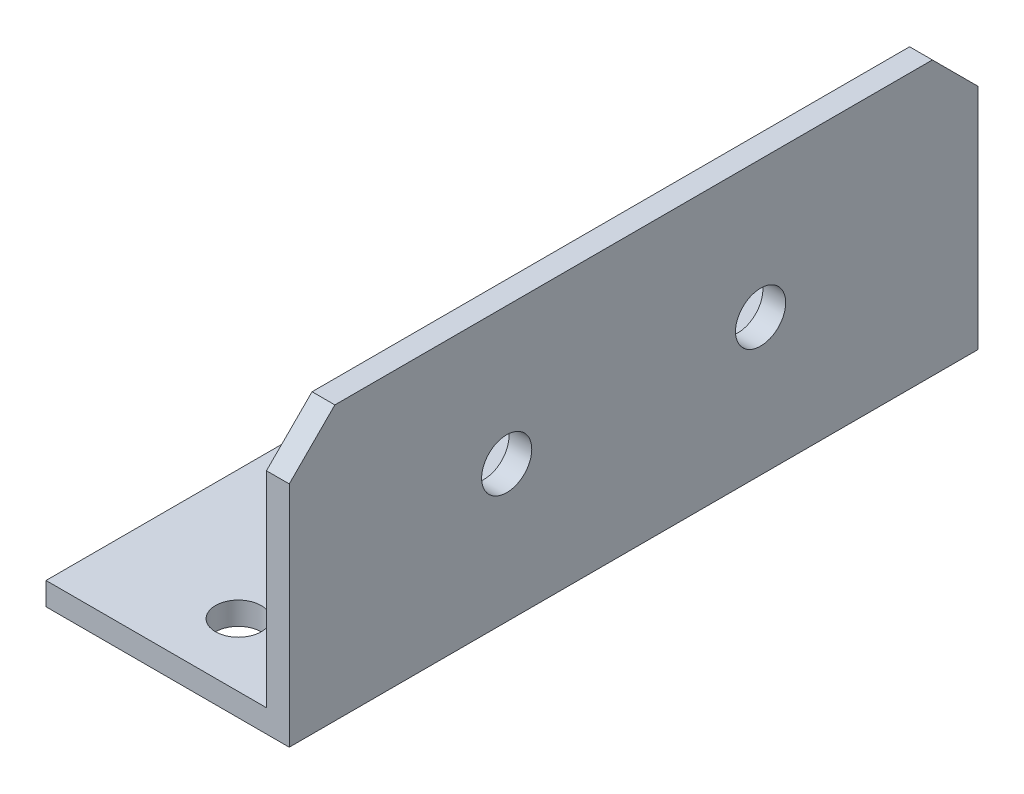
SolidWorks part; units mm, degrees
ref_plane "Front Plane" through (0, 0, 0) normal (0, 0, 1) x (1, 0, 0)
ref_plane "Top Plane" through (0, 0, 0) normal (0, 1, 0) x (1, 0, 0)
ref_plane "Right Plane" through (0, 0, 0) normal (1, 0, 0) x (0, 0, -1)
sketch "Sketch1" plane through (0, 0, 0) normal (0, 0, 1) x (1, 0, 0)
  line L0 (0, 0) -> (0, 18)
  line L1 (0, 0) -> (-16, 0)
  line L2 (-1.5, 1.5) -> (-16, 1.5)
  line L3 (-1.5, 1.5) -> (-1.5, 18)
  line L4 (-1.5, 18) -> (0, 18)
  line L5 (-16, 1.5) -> (-16, 0)
  dimension "D1" = 16
  dimension "D2" = 18
  dimension "D3" = 1.5
extrude "Boss-Extrude1" add sketch "Sketch1" along normal blind 45.3 contours L1 L5 L2 L3 L4 L0
sketch "Sketch2" plane through (-1.5, 3, 0) normal (-1, 0, 0) x (0, 1, 0)
  line L0 (15, -22.65) -> (-1.5, -22.65) construction
  line L1 (12, -45.3) -> (15, -42.3)
  line L2 (-1.5, -45.3) -> (15, -45.3) construction
  line L3 (15, -45.3) -> (15, 0) construction
  line L4 (-1.5, -45.3) -> (-1.5, 0) construction
  line L5 (12, 0) -> (15, -3)
  circle A0 centre (6, -31) radius 1.65
  circle A1 centre (6, -14.3) radius 1.65
  line M8 (15, 0) -> (-1.5, 0)
  line M10 (-1.5, -45.3) -> (15, -45.3)
  line M11 (15, -45.3) -> (15, 0)
  dimension "D1" = 3.3
  dimension "D2" = 8.35
  dimension "D3" = 9
  dimension "D4" = 3
  dimension "D5" = 45
extrude "Cut-Extrude1" cut sketch "Sketch2" against normal through all contours L5 M8 M11 | L1 M10 M11 | A1 | A0 region at (-1.5, 17, 1) region at (-1.5, 17, 44.3)
sketch "Sketch3" plane through (0, 1.5, 0) normal (0, 1, 0) x (1, 0, 0)
  line L1 (-1.5, -22.65) -> (-16, -22.65) construction
  line L2 (-1.5, -45.3) -> (-1.5, 0) construction
  line L3 (-16, -45.3) -> (-16, 0) construction
  circle A0 centre (-7.5, -4.15) radius 1.5
  circle A1 centre (-7.5, -41.15) radius 1.5
  dimension "D1" = 3
  dimension "D2" = 18.5
  dimension "D3" = 6
extrude "Cut-Extrude2" cut sketch "Sketch3" against normal through all
ref_axis "Axis1" through (0, 18, 22.65) along (0, -1, 0)
